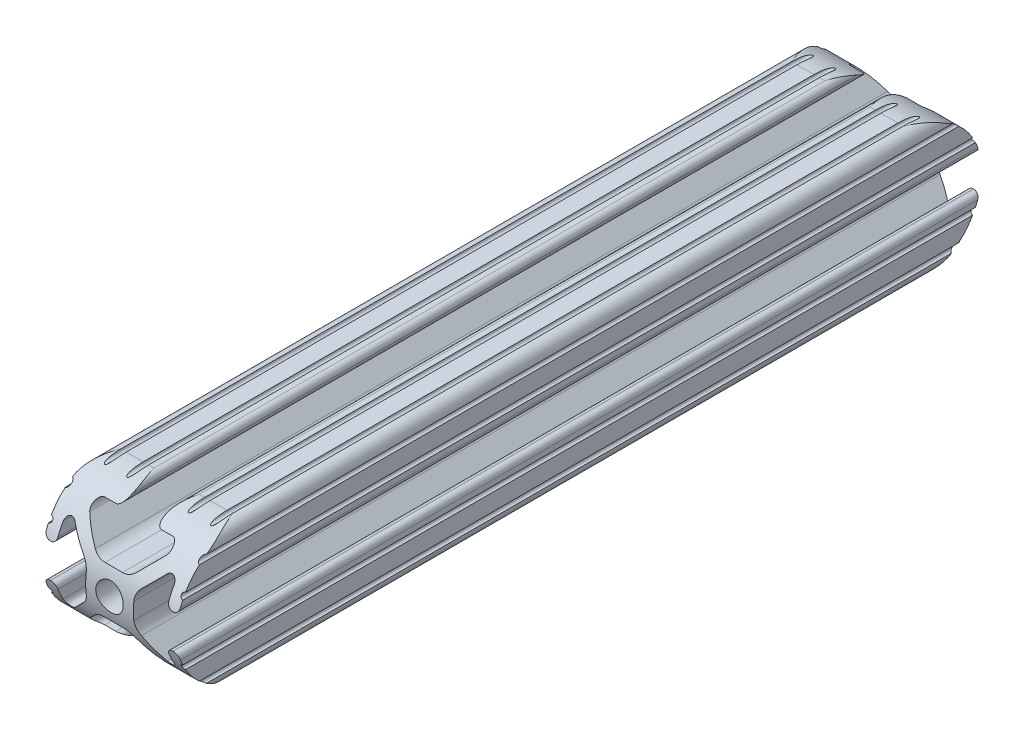
SolidWorks part; units mm, degrees
material "6061-T6 (SS)"
ref_plane "Front Plane" through (0, 0, 0) normal (0, 0, 1) x (1, 0, 0)
ref_plane "Top Plane" through (0, 0, 0) normal (0, 1, 0) x (1, 0, 0)
ref_plane "Right Plane" through (0, 0, 0) normal (1, 0, 0) x (0, 0, -1)
sketch "Sketch1" plane through (0, 0, 0) normal (0, 0, 1) x (1, 0, 0)
  line L88 (-7.1797, -8.6452) -> (-3.9523, -5.4237)
  line L89 (-1.7093, -4.4958) -> (1.7093, -4.4958)
  line L90 (3.9523, -5.4237) -> (7.1797, -8.6452)
  line L91 (6.4164, -10.4902) -> (4.2875, -10.4902)
  line L92 (3.2385, -11.5392) -> (3.2385, -11.651)
  line L93 (4.2875, -12.7) -> (5.3171, -12.7)
  line L94 (6.3331, -12.7) -> (9.5504, -12.7)
  line L95 (12.7, -9.5504) -> (12.7, -6.3331)
  line L96 (12.7, -5.3171) -> (12.7, -4.2875)
  line L97 (11.651, -3.2385) -> (11.5392, -3.2385)
  line L98 (10.4902, -4.2875) -> (10.4902, -6.4021)
  line L99 (8.7371, -7.1294) -> (5.441, -3.8408)
  line L100 (4.5085, -1.5932) -> (4.5085, 1.5932)
  line L101 (5.441, 3.8408) -> (8.7371, 7.1294)
  line L102 (10.4902, 6.4021) -> (10.4902, 4.2875)
  line L103 (11.5392, 3.2385) -> (11.651, 3.2385)
  line L104 (12.7, 4.2875) -> (12.7, 5.3171)
  line L105 (12.7, 6.3331) -> (12.7, 9.5504)
  line L106 (9.5504, 12.7) -> (6.3331, 12.7)
  line L107 (5.3171, 12.7) -> (4.2875, 12.7)
  line L108 (3.2385, 11.651) -> (3.2385, 11.5392)
  line L109 (4.2875, 10.4902) -> (6.4768, 10.4902)
  line L110 (7.207, 8.7244) -> (3.8983, 5.4232)
  line L111 (1.6558, 4.4958) -> (-1.6558, 4.4958)
  line L112 (-3.8983, 5.4232) -> (-7.207, 8.7244)
  line L113 (-6.4768, 10.4902) -> (-4.2875, 10.4902)
  line L114 (-3.2385, 11.5392) -> (-3.2385, 11.651)
  line L115 (-4.2875, 12.7) -> (-5.3171, 12.7)
  line L116 (-6.3331, 12.7) -> (-9.5504, 12.7)
  line L117 (-12.7, 9.5504) -> (-12.7, 6.3331)
  line L118 (-12.7, 5.3171) -> (-12.7, 4.2875)
  line L119 (-11.651, 3.2385) -> (-11.5392, 3.2385)
  line L120 (-10.4902, 4.2875) -> (-10.4902, 6.4021)
  line L121 (-8.7371, 7.1294) -> (-5.441, 3.8408)
  line L122 (-4.5085, 1.5932) -> (-4.5085, -1.5932)
  line L123 (-5.441, -3.8408) -> (-8.7371, -7.1294)
  line L124 (-10.4902, -6.4021) -> (-10.4902, -4.2875)
  line L125 (-11.5392, -3.2385) -> (-11.651, -3.2385)
  line L126 (-12.7, -4.2875) -> (-12.7, -5.3171)
  line L127 (-12.7, -6.3331) -> (-12.7, -9.5504)
  line L128 (-9.5504, -12.7) -> (-6.3331, -12.7)
  line L129 (-5.3171, -12.7) -> (-4.2875, -12.7)
  line L130 (-3.2385, -11.651) -> (-3.2385, -11.5392)
  line L131 (-4.2875, -10.4902) -> (-6.4164, -10.4902)
  circle A1 centre (0, 0) radius 2.6035
  arc A104 (-7.1797, -8.6452) -> (-6.4164, -10.4902) centre (-6.4164, -9.4098) ccw
  arc A105 (-1.7093, -4.4958) -> (-3.9523, -5.4237) centre (-1.7093, -7.6708) ccw
  arc A106 (3.9523, -5.4237) -> (1.7093, -4.4958) centre (1.7093, -7.6708) ccw
  arc A107 (6.4164, -10.4902) -> (7.1797, -8.6452) centre (6.4164, -9.4098) ccw
  arc A108 (4.2875, -10.4902) -> (3.2385, -11.5392) centre (4.2875, -11.5392) ccw
  arc A109 (3.2385, -11.651) -> (4.2875, -12.7) centre (4.2875, -11.651) ccw
  arc A110 (6.3331, -12.7) -> (5.3171, -12.7) centre (5.8251, -12.7) ccw
  arc A111 (10.5664, -12.6998) -> (9.5504, -12.7) centre (10.0584, -12.7) ccw
  arc A112 (10.5664, -12.6998) -> (12.6998, -10.5664) centre (10.5918, -10.5918) ccw
  arc A113 (12.7, -9.5504) -> (12.6998, -10.5664) centre (12.7, -10.0584) ccw
  arc A114 (12.7, -5.3171) -> (12.7, -6.3331) centre (12.7, -5.8251) ccw
  arc A115 (12.7, -4.2875) -> (11.651, -3.2385) centre (11.651, -4.2875) ccw
  arc A116 (11.5392, -3.2385) -> (10.4902, -4.2875) centre (11.5392, -4.2875) ccw
  arc A117 (8.7371, -7.1294) -> (10.4902, -6.4021) centre (9.4628, -6.4021) ccw
  arc A118 (4.5085, -1.5932) -> (5.441, -3.8408) centre (7.6835, -1.5932) ccw
  arc A119 (5.441, 3.8408) -> (4.5085, 1.5932) centre (7.6835, 1.5932) ccw
  arc A120 (10.4902, 6.4021) -> (8.7371, 7.1294) centre (9.4628, 6.4021) ccw
  arc A121 (10.4902, 4.2875) -> (11.5392, 3.2385) centre (11.5392, 4.2875) ccw
  arc A122 (11.651, 3.2385) -> (12.7, 4.2875) centre (11.651, 4.2875) ccw
  arc A123 (12.7, 6.3331) -> (12.7, 5.3171) centre (12.7, 5.8251) ccw
  arc A124 (12.6998, 10.5664) -> (12.7, 9.5504) centre (12.7, 10.0584) ccw
  arc A125 (12.6998, 10.5664) -> (10.5664, 12.6998) centre (10.5918, 10.5918) ccw
  arc A126 (9.5504, 12.7) -> (10.5664, 12.6998) centre (10.0584, 12.7) ccw
  arc A127 (5.3171, 12.7) -> (6.3331, 12.7) centre (5.8251, 12.7) ccw
  arc A128 (4.2875, 12.7) -> (3.2385, 11.651) centre (4.2875, 11.651) ccw
  arc A129 (3.2385, 11.5392) -> (4.2875, 10.4902) centre (4.2875, 11.5392) ccw
  arc A130 (7.207, 8.7244) -> (6.4768, 10.4902) centre (6.4768, 9.4563) ccw
  arc A131 (1.6558, 4.4958) -> (3.8983, 5.4232) centre (1.6558, 7.6708) ccw
  arc A132 (-3.8983, 5.4232) -> (-1.6558, 4.4958) centre (-1.6558, 7.6708) ccw
  arc A133 (-6.4768, 10.4902) -> (-7.207, 8.7244) centre (-6.4768, 9.4563) ccw
  arc A134 (-4.2875, 10.4902) -> (-3.2385, 11.5392) centre (-4.2875, 11.5392) ccw
  arc A135 (-3.2385, 11.651) -> (-4.2875, 12.7) centre (-4.2875, 11.651) ccw
  arc A136 (-6.3331, 12.7) -> (-5.3171, 12.7) centre (-5.8251, 12.7) ccw
  arc A137 (-10.5664, 12.6998) -> (-9.5504, 12.7) centre (-10.0584, 12.7) ccw
  arc A138 (-10.5664, 12.6998) -> (-12.6998, 10.5664) centre (-10.5918, 10.5918) ccw
  arc A139 (-12.7, 9.5504) -> (-12.6998, 10.5664) centre (-12.7, 10.0584) ccw
  arc A140 (-12.7, 5.3171) -> (-12.7, 6.3331) centre (-12.7, 5.8251) ccw
  arc A141 (-12.7, 4.2875) -> (-11.651, 3.2385) centre (-11.651, 4.2875) ccw
  arc A142 (-11.5392, 3.2385) -> (-10.4902, 4.2875) centre (-11.5392, 4.2875) ccw
  arc A143 (-8.7371, 7.1294) -> (-10.4902, 6.4021) centre (-9.4628, 6.4021) ccw
  arc A144 (-4.5085, 1.5932) -> (-5.441, 3.8408) centre (-7.6835, 1.5932) ccw
  arc A145 (-5.441, -3.8408) -> (-4.5085, -1.5932) centre (-7.6835, -1.5932) ccw
  arc A146 (-10.4902, -6.4021) -> (-8.7371, -7.1294) centre (-9.4628, -6.4021) ccw
  arc A147 (-10.4902, -4.2875) -> (-11.5392, -3.2385) centre (-11.5392, -4.2875) ccw
  arc A148 (-11.651, -3.2385) -> (-12.7, -4.2875) centre (-11.651, -4.2875) ccw
  arc A149 (-12.7, -6.3331) -> (-12.7, -5.3171) centre (-12.7, -5.8251) ccw
  arc A150 (-12.6998, -10.5664) -> (-12.7, -9.5504) centre (-12.7, -10.0584) ccw
  arc A151 (-12.6998, -10.5664) -> (-10.5664, -12.6998) centre (-10.5918, -10.5918) ccw
  arc A152 (-9.5504, -12.7) -> (-10.5664, -12.6998) centre (-10.0584, -12.7) ccw
  arc A153 (-5.3171, -12.7) -> (-6.3331, -12.7) centre (-5.8251, -12.7) ccw
  arc A154 (-4.2875, -12.7) -> (-3.2385, -11.651) centre (-4.2875, -11.651) ccw
  arc A155 (-3.2385, -11.5392) -> (-4.2875, -10.4902) centre (-4.2875, -11.5392) ccw
extrude "Boss-Extrude1" add sketch "Sketch1" along normal mid plane 152.4
sketch "Sketch3" plane through (12.7, 0, 0) normal (1, 0, 0) x (0, 0, -1)
  line L0 (-76.2, 0) -> (76.2, 0) construction
  line L1 (-76.2, 12.7) -> (76.2, 12.7)
  line L2 (-76.2, 12.7) -> (-76.2, -12.7)
  line L3 (-76.2, -12.7) -> (76.2, -12.7)
  line L4 (76.2, 12.7) -> (76.2, -12.7)
  circle A0 centre (-63.5, 0) radius 12.7
  circle A1 centre (63.5, 0) radius 12.7
  circle A2 centre (-63.5, 0) radius 3.175
  circle A3 centre (-38.1, 0) radius 3.175
  line M9 (76.2, 6.3331) -> (76.2, 9.5504)
  line M10 (76.2, 9.5504) -> (-76.2, 9.5504)
  line M11 (-76.2, 9.5504) -> (-76.2, 6.3331)
  line M12 (-76.2, 6.3331) -> (76.2, 6.3331)
  dimension "D1" = 25.4
  dimension "D2" = 6.35
extrude "Cut-Extrude1" cut sketch "Sketch3" against normal through all both and the other way through all contours A0 L2 L3 | A0 M10 M11 M12 | A0 L1 L2 M10 | A0 L2 M12 | L0 A3 | A3 L0 | A2 L0 | L0 A2 | A1 L4 L1 M10 | A1 M12 M9 M10 | A1 L4 M12 | A1 L3 L4 region at (12.7, -1.3475, 63.5) region at (12.7, 1.3475, 63.5) region at (12.7, 1.3475, 38.1) region at (12.7, -1.3475, 38.1) region at (12.7, -9.8632, 73.3632) region at (12.7, 4.7717, 75.6989) region at (12.7, 8.1865, 74.6688) region at (12.7, -9.8632, -73.3632) region at (12.7, 11.3727, 72.4456) region at (12.7, 4.7717, -75.6989) region at (12.7, 8.1865, -74.6688) region at (12.7, 11.3727, -72.4456)
